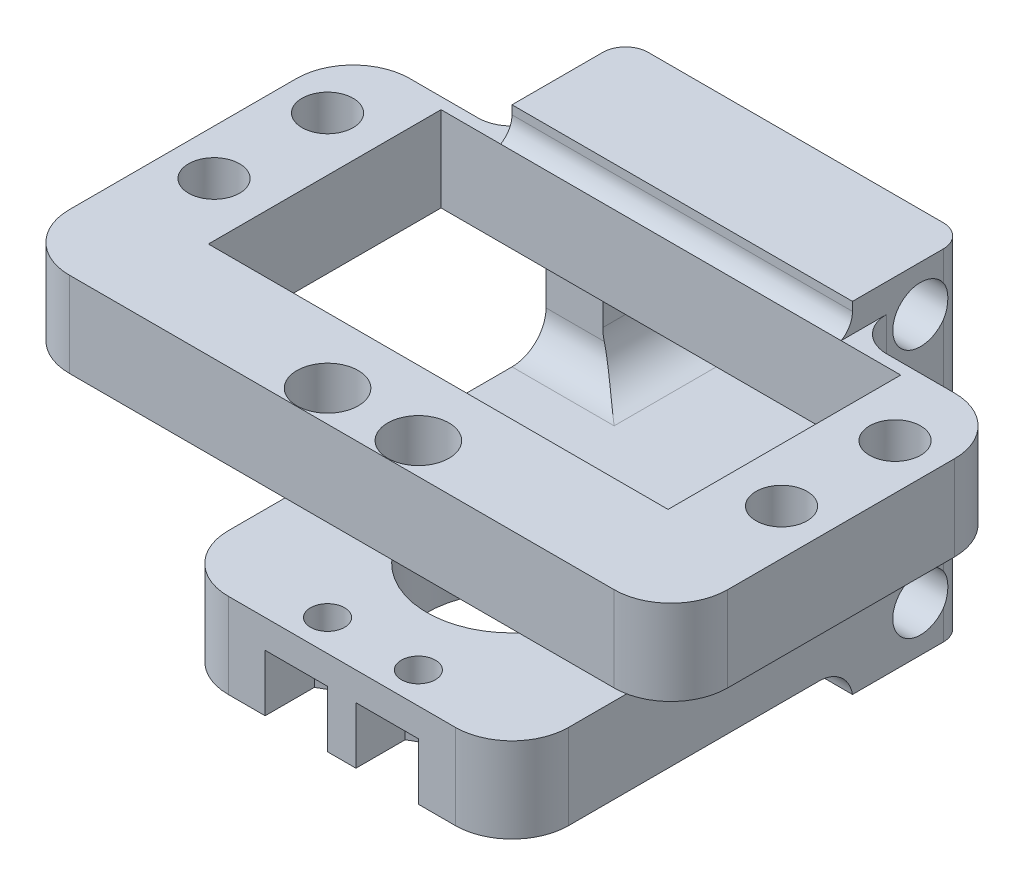
SolidWorks part; units mm, degrees
material "ABS"
ref_plane "Ebene vorne" through (0, 0, 0) normal (0, 0, 1) x (1, 0, 0)
ref_plane "Ebene oben" through (0, 0, 0) normal (0, 1, 0) x (1, 0, 0)
ref_plane "Ebene rechts" through (0, 0, 0) normal (1, 0, 0) x (0, 0, -1)
sketch "Skizze1" plane through (0, 0, 0) normal (0, 1, 0) x (1, 0, 0)
  line L0 (0, 0) -> (0, -32.6471) construction
  line L1 (-15, 0) -> (15, 0)
  line L2 (-15, 0) -> (-15, -10)
  line L3 (-15, -10) -> (15, -10)
  line L4 (15, 0) -> (15, -10)
  dimension "D1" = 30
  dimension "D2" = 10
extrude "Aufsatz-Linear austragen1" add sketch "Skizze1" along normal mid plane 30
sketch "Skizze3" plane through (0, 0, 0) normal (0, 1, 0) x (1, 0, 0)
  line L0 (0, 0) -> (0, -35.0207) construction
  line L1 (-13.25, 0) -> (13.25, 0) construction
  line L2 (-15, -10) -> (15, -10) construction
  line L3 (29, -35) -> (-29, -35)
  line L4 (29, -35) -> (29, -10)
  line L5 (29, -10) -> (-29, -10)
  line L6 (-29, -35) -> (-29, -10)
  line L7 (29, -35) -> (-29, -10) construction
  line L8 (29, -10) -> (-29, -35) construction
  point P4 (0, -22.5)
  dimension "D1" = 58
  dimension "D2" = 25
extrude "Aufsatz-Linear austragen2" add sketch "Skizze3" along normal mid plane 25
sketch "Skizze4" plane through (0, 0, 35) normal (0, 0, 1) x (1, 0, 0)
  line L0 (-29, 12.5) -> (-29, -12.5) construction
  line L1 (29, -5) -> (-29, -5)
  line L2 (29, -5) -> (29, 5)
  line L3 (29, 5) -> (-29, 5)
  line L4 (-29, -5) -> (-29, 5)
  line L5 (29, -5) -> (-29, 5) construction
  line L6 (29, 5) -> (-29, -5) construction
  point P0 (0, 0)
  dimension "D1" = 10
extrude "Schnitt-Linear austragen1" cut sketch "Skizze4" against normal blind 28
sketch "Skizze5" plane through (0, 15, 0) normal (0, 1, 0) x (1, 0, 0)
  line L0 (0, 0) -> (0, -38.083) construction
  line L1 (20.25, -31.5) -> (-20.25, -31.5)
  line L2 (20.25, -31.5) -> (20.25, -11)
  line L3 (20.25, -11) -> (-20.25, -11)
  line L4 (-20.25, -31.5) -> (-20.25, -11)
  line L5 (20.25, -31.5) -> (-20.25, -11) construction
  line L6 (20.25, -11) -> (-20.25, -31.5) construction
  line L7 (15, 0) -> (-15, 0) construction
  line L8 (0, -21.25) -> (37.4905, -21.25) construction
  line L9 (-15, -10) -> (-29, -10) construction
  point P0 (0, -21.25)
  dimension "D1" = 40.5
  dimension "D2" = 1
  dimension "D3" = 20.5
extrude "Schnitt-Linear austragen2" cut sketch "Skizze5" against normal up to surface (10 mm away) up to face at (0, 5, 15.5)
sketch "Skizze6" plane through (0, 15, 0) normal (0, 1, 0) x (1, 0, 0)
  line L0 (0, -16.5) -> (0, 16.5) construction
  line L1 (-20.25, -21.25) -> (20.25, -21.25) construction
  line L2 (-20.25, -11) -> (-20.25, -31.5) construction
  line L3 (20.25, -31.5) -> (20.25, -11) construction
  circle A0 centre (-25, -16.25) radius 2.25
  circle A1 centre (-25, -26.25) radius 2.25
  circle A2 centre (25, -26.25) radius 2.25
  circle A3 centre (25, -16.25) radius 2.25
  dimension "D1" = 4.5
  dimension "D2" = 10
  dimension "D3" = 50
extrude "Schnitt-Linear austragen3" cut sketch "Skizze6" against normal up to next
sketch "Skizze7" plane through (0, -15, 0) normal (0, -1, 0) x (1, 0, 0)
  line L0 (-15, 10) -> (-29, 10) construction
  line L1 (-29, 35) -> (-15, 35)
  line L2 (-29, 35) -> (-29, 10)
  line L3 (-29, 10) -> (-15, 10)
  line L4 (-15, 35) -> (-15, 10)
  line L9 (0, -16.5) -> (0, 16.5) construction
  line L10 (15, 35) -> (15, 10)
  line L11 (29, 10) -> (15, 10)
  line L12 (29, 35) -> (29, 10)
  line L13 (29, 35) -> (15, 35)
extrude "Schnitt-Linear austragen4" cut sketch "Skizze7" against normal up to next
sketch "Skizze8" plane through (0, 5, 0) normal (0, -1, 0) x (-1, 0, 0)
  line L0 (0, 16.5) -> (0, -16.5) construction
  line L1 (25, -30.2915) -> (28.5, -28.2707)
  line L2 (28.5, -28.2707) -> (28.5, -24.2293)
  line L3 (28.5, -24.2293) -> (25, -22.2085)
  line L4 (25, -22.2085) -> (21.5, -24.2293)
  line L5 (21.5, -24.2293) -> (21.5, -28.2707)
  line L6 (21.5, -28.2707) -> (25, -30.2915)
  line L7 (20.25, -21.25) -> (-20.25, -21.25) construction
  line L8 (20.25, -31.5) -> (20.25, -11) construction
  line L9 (-20.25, -11) -> (-20.25, -31.5) construction
  line L10 (21.5, -14.2293) -> (25, -12.2085)
  line L11 (21.5, -18.2707) -> (21.5, -14.2293)
  line L12 (25, -20.2915) -> (21.5, -18.2707)
  line L13 (28.5, -18.2707) -> (25, -20.2915)
  line L14 (28.5, -14.2293) -> (28.5, -18.2707)
  line L15 (25, -12.2085) -> (28.5, -14.2293)
  line L16 (-25, -12.2085) -> (-28.5, -14.2293)
  line L17 (-28.5, -14.2293) -> (-28.5, -18.2707)
  line L18 (-28.5, -18.2707) -> (-25, -20.2915)
  line L19 (-25, -20.2915) -> (-21.5, -18.2707)
  line L20 (-21.5, -18.2707) -> (-21.5, -14.2293)
  line L21 (-21.5, -14.2293) -> (-25, -12.2085)
  line L22 (-21.5, -28.2707) -> (-25, -30.2915)
  line L23 (-21.5, -24.2293) -> (-21.5, -28.2707)
  line L24 (-25, -22.2085) -> (-21.5, -24.2293)
  line L25 (-28.5, -24.2293) -> (-25, -22.2085)
  line L26 (-28.5, -28.2707) -> (-28.5, -24.2293)
  line L27 (-25, -30.2915) -> (-28.5, -28.2707)
  circle A0 centre (25, -26.25) radius 3.5 construction
  circle A1 centre (25, -16.25) radius 3.5 construction
  circle A2 centre (-25, -16.25) radius 3.5 construction
  circle A3 centre (-25, -26.25) radius 3.5 construction
  dimension "D1" = 7
extrude "Schnitt-Linear austragen5" cut sketch "Skizze8" against normal blind 4
fillet "Verrundung2" radius 3 2 edges at (15, 8.75, 10) (-15, 8.75, 10)
fillet "Verrundung3" radius 3 3 edges at (0, -5, 7) (0, 5, 7) (0, -12.5, 10)
fillet "Verrundung4" radius 2 1 edges at (0, 12.5, 10)
sketch "Skizze9" plane through (0, -5, 0) normal (0, 1, 0) x (1, 0, 0)
  line L0 (-20.25, -21.25) -> (20.25, -21.25) construction
  line L1 (-20.25, -11) -> (-20.25, -31.5) construction
  line L2 (20.25, -31.5) -> (20.25, -11) construction
  line L4 (-25, -16.25) -> (-25, -26.25) construction
  line L5 (0, -16.5) -> (0, 16.5) construction
  line L6 (25, -16.25) -> (25, -26.25) construction
  circle A0 centre (-10, -21.25) radius 1.5
  circle A1 centre (10, -21.25) radius 1.5
  circle A2 centre (-10, -21.25) radius 10 construction
  circle A3 centre (10, -21.25) radius 10 construction
  point P8 (-25, -21.25)
  dimension "D1" = 3
  dimension "D2" = 15
extrude "Schnitt-Linear austragen6" cut sketch "Skizze9" against normal through all
sketch "Skizze10" plane through (0, -5, 0) normal (0, 1, 0) x (1, 0, 0)
  circle A0 centre (-10, -21.25) radius 3
  circle A1 centre (10, -21.25) radius 3
  dimension "D1" = 6
  dimension "D2" = 6
extrude "Schnitt-Linear austragen7" [suppressed] cut sketch "Skizze10" against normal blind 3
sketch "Skizze11" plane through (0, 0, 35) normal (0, 0, 1) x (1, 0, 0)
  line L0 (15, -5) -> (-15, -5) construction
  line L1 (-15, -5) -> (-15, -12.5) construction
  line L2 (-15, -12.5) -> (15, -12.5) construction
  line L3 (15, -12.5) -> (15, -5) construction
  line L4 (-29, 12.5) -> (-29, 5) construction
  line L5 (-29, 5) -> (29, 5) construction
  line L6 (29, 5) -> (29, 12.5) construction
  line L7 (29, 12.5) -> (-29, 12.5) construction
  line L8 (15, -5) -> (-15, -5)
  line L9 (-15, -5) -> (-15, -12.5)
  line L10 (-15, -12.5) -> (15, -12.5)
  line L11 (15, -12.5) -> (15, -5)
  line L12 (-29, 12.5) -> (-29, 5)
  line L13 (-29, 5) -> (29, 5)
  line L14 (29, 5) -> (29, 12.5)
  line L15 (29, 12.5) -> (-29, 12.5)
extrude "Aufsatz-Linear austragen3" add sketch "Skizze11" along normal blind 5
sketch "Skizze12" plane through (0, 12.5, 0) normal (0, 1, 0) x (1, 0, 0)
  line L0 (-10, -21.25) -> (-4, -37.25) construction
  line L1 (-4, -37.25) -> (-4, -21.25) construction
  line L2 (-4, -21.25) -> (-10, -21.25) construction
  line L3 (0, -16.5) -> (0, 16.5) construction
  line L4 (4, -37.25) -> (4, -21.25) construction
  line L5 (10, -21.25) -> (4, -37.25) construction
  circle A0 centre (-4, -37.25) radius 1.5
  circle A1 centre (4, -37.25) radius 1.5
  dimension "D1" = 3
  dimension "D2" = 6
  dimension "D3" = 16
extrude "Schnitt-Linear austragen8" cut sketch "Skizze12" against normal through all both and the other way through all
fillet "Verrundung5" radius 5 6 edges at (-29, 8.75, 10) (29, 8.75, 10) (15, -8.75, 40) (-15, -8.75, 40) (29, 8.75, 40) (-29, 8.75, 40)
sketch "Skizze13" plane through (0, 12.5, 0) normal (0, 1, 0) x (1, 0, 0)
  circle A0 centre (-4, -37.25) radius 2.7
  circle A1 centre (4, -37.25) radius 2.7
  dimension "D1" = 5.4
extrude "Schnitt-Linear austragen9" cut sketch "Skizze13" against normal blind 5
sketch "Skizze14" plane through (0, -12.5, 0) normal (0, -1, 0) x (1, 0, 0)
  line L0 (-6.75, 45) -> (-1.25, 45)
  line L2 (-6.75, 45) -> (-6.75, 35.6623)
  line L3 (-6.75, 35.6623) -> (-4, 34.0746)
  line L4 (-4, 34.0746) -> (-1.25, 35.6623)
  line L5 (-1.25, 35.6623) -> (-1.25, 45)
  line L8 (1.25, 45) -> (1.25, 35.6623)
  line L9 (1.25, 35.6623) -> (4, 34.0746)
  line L10 (4, 34.0746) -> (6.75, 35.6623)
  line L11 (6.75, 35.6623) -> (6.75, 45)
  line L13 (-1.25, 38.8377) -> (-4, 40.4254) [skipped]
  line L14 (-4, 40.4254) -> (-6.75, 38.8377) [skipped]
  line L15 (6.75, 38.8377) -> (4, 40.4254) [skipped]
  line L16 (4, 40.4254) -> (1.25, 38.8377) [skipped]
  line L17 (1.25, 45) -> (6.75, 45)
  circle A0 centre (-4, 37.25) radius 2.75 construction
  circle A1 centre (4, 37.25) radius 2.75 construction
  dimension "D1" = 5.5
  dimension "D2" = 45
extrude "Schnitt-Linear austragen10" cut sketch "Skizze14" against normal blind 5
fillet "Verrundung6" radius 2 2 edges at (15, 0, 0) (-15, 0, 0)
sketch "Skizze16" plane through (0, 0, 0) normal (1, 0, 0) x (0, 0, -1)
  line L0 (22, 0) -> (-22, 0) construction
  circle A0 centre (-4, 11) radius 1.75
  circle A1 centre (-4, -11) radius 1.75
  dimension "D3" = 3.5
  dimension "D1" = 11
  dimension "D2" = 4
extrude "Schnitt-Linear austragen11" cut sketch "Skizze16" against normal through all both and the other way through all
sketch "Skizze17" plane through (15, 0, 0) normal (1, 0, 0) x (0, 0, -1)
  line L0 (22, 0) -> (-22, 0) construction
  circle A0 centre (-4, 11) radius 2.45
  circle A1 centre (-4, -11) radius 2.45
  dimension "D1" = 4.9
extrude "Schnitt-Linear austragen12" cut sketch "Skizze17" against normal blind 5.7
mirror "Spiegeln1" about plane through (0, 0, 0) normal (1, 0, 0) of "Schnitt-Linear austragen12"
sketch "Skizze19" plane through (0, 0, 7) normal (0, 0, 1) x (1, 0, 0)
  line L1 (10, -5) -> (-10, -5)
  line L2 (10, -5) -> (10, 5)
  line L3 (10, 5) -> (-10, 5)
  line L4 (-10, -5) -> (-10, 5)
  line L5 (-10, -5) -> (-10, -12.5) construction
  line L6 (-18, 5) -> (18, 5) construction
extrude "Schnitt-Linear austragen13" cut sketch "Skizze19" against normal through all both and the other way through all
fillet "Verrundung8" radius 4 4 edges at (-10, -5, 5) (-10, 5, 5) (10, -5, 5) (10, 5, 5)
sketch "Skizze21" plane through (0, -12.5, 0) normal (0, -1, 0) x (1, 0, 0)
  circle A0 centre (0, 25) radius 7.5
  dimension "D1" = 15
  dimension "D2" = 25
extrude "Schnitt-Linear austragen15" cut sketch "Skizze21" against normal up to next
sketch "Skizze22" plane through (0, -12.5, 0) normal (0, -1, 0) x (1, 0, 0)
  line L0 (0, -16.5) -> (0, 16.5) construction
  circle A0 centre (-10, 21.25) radius 3
  circle A1 centre (10, 21.25) radius 3
  dimension "D1" = 6
extrude "Schnitt-Linear austragen16" cut sketch "Skizze22" against normal blind 3
